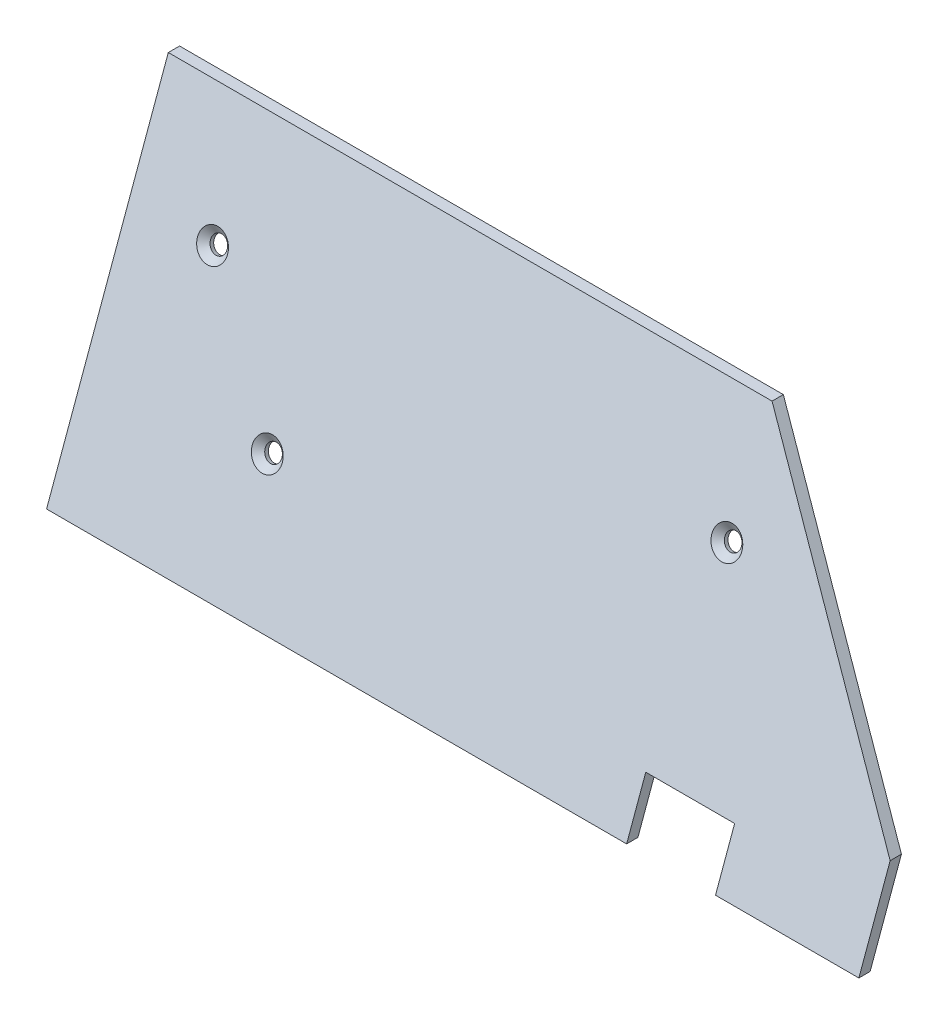
SolidWorks part; units mm, degrees
ref_plane "Front Plane" through (0, 0, 0) normal (0, 0, 1) x (1, 0, 0)
ref_plane "Top Plane" through (0, 0, 0) normal (0, 1, 0) x (1, 0, 0)
ref_plane "Right Plane" through (0, 0, 0) normal (1, 0, 0) x (0, 0, -1)
sketch "Sketch1" plane through (0, 0, 0) normal (1, 0, 0) x (0, 0, -1)
  line L0 (0, 0) -> (-2.3622, 0)
  line L1 (-2.3622, 0) -> (23.1157, 70)
  line L2 (23.1157, 70) -> (25.4779, 70)
  line L3 (25.4779, 70) -> (0, 0)
  dimension "D1" = 2.3622
  dimension "D2" = 2.3622
  dimension "D3" = 70
  dimension "D4" = 70
extrude "Main" add sketch "Sketch1" along normal mid plane 170
hole_wizard "BackBracketHoles" positions "Sketch2" profile "Sketch3" countersink size "M3" standard "ANSI Metric"
sketch "Sketch2" plane through (0, 0.7592, 2.0859) normal (0, 0.342, 0.9397) x (1, 0, 0)
  line L0 (-85, 73.6845) -> (-85, -0.8079) construction
  line L1 (85, -0.8079) -> (-85, -0.8079) construction
  point P0 (-67.6378, 50.0021)
  point P2 (-47.6378, 25.0021)
  dimension "D1" = 17.3622
  dimension "D2" = 50.81
  dimension "D3" = 25.81
  dimension "D4" = 37.3622
sketch "Sketch3" plane through (-67.6378, 47.7458, -15.0158) normal (1, 0, 0) x (0, -0.9397, 0.342)
  line L0 (0, 0) -> (0, 5)
  line L1 (0, 5) -> (1.75, 5)
  line L2 (1.75, 5) -> (1.75, 1.4)
  line L3 (1.75, 1.4) -> (3.15, 0)
  line L5 (3.15, 0) -> (0, 0)
  line L6 (-1.75, 1.4) -> (-3.15, 0) construction
  line L10 (0, 5) -> (-1.75, 5) construction
  line L11 (0, -6.35) -> (0, 107.95) construction
  dimension "Hole Dia." = 3.5
  dimension "Hole Depth" = 5
  dimension "Near C'Sink Dia." = 6.3
  dimension "Near C'Sink Angle" = 90
  dimension "Drill Angle" = 180
sketch "Sketch4" plane through (0, 0, 0) normal (0, 0, 1) x (1, 0, 0)
  line L0 (85.1927, 0.1116) -> (100, 0.1116)
  line L1 (100, 0.1116) -> (41.3567, 70)
  line L2 (85, 70) -> (-85, 70) construction
  line L3 (41.3567, 70) -> (41.3567, 0)
  line L4 (85, 0) -> (-85, 0) construction
  line L5 (41.3567, 0) -> (85.1927, 0.1116)
  line L6 (100, 0.1116) -> (100, 70)
  line L7 (100, 70) -> (41.3567, 70)
  line L8 (85, 70) -> (85, 0) construction
  dimension "D1" = 50
  dimension "D2" = 15
extrude "Cut-Extrude1" cut sketch "Sketch4" against normal blind 28.6 contours L6 L7 L1 region at (80.4522, 46.7039, 0)
hole_wizard "CSK for M3 Flat Head Machine Screw1" positions "Sketch5" profile "Sketch6" countersink size "M3" standard "ANSI Metric"
sketch "Sketch5" plane through (0, 0.7592, 2.0859) normal (0, 0.342, 0.9397) x (1, 0, 0)
  line L0 (30, 60.0021) -> (52.6886, 60.0021) construction
  line L1 (30, 60.0021) -> (30, 32.9616) construction
  point P0 (40, 50.0021)
  dimension "D1" = 10
  dimension "D2" = 10
sketch "Sketch6" plane through (40, 47.7458, -15.0158) normal (1, 0, 0) x (0, -0.9397, 0.342)
  line L0 (0, 0) -> (0, 5)
  line L1 (0, 5) -> (1.75, 5)
  line L2 (1.75, 5) -> (1.75, 1.4)
  line L3 (1.75, 1.4) -> (3.15, 0)
  line L5 (3.15, 0) -> (0, 0)
  line L6 (-1.75, 1.4) -> (-3.15, 0) construction
  line L10 (0, 5) -> (-1.75, 5) construction
  line L11 (0, -6.35) -> (0, 107.95) construction
  dimension "Hole Dia." = 3.5
  dimension "Hole Depth" = 5
  dimension "Near C'Sink Dia." = 6.3
  dimension "Near C'Sink Angle" = 90
  dimension "Drill Angle" = 180
sketch "Sketch7" plane through (0, 0, 0) normal (0, 0, 1) x (1, 0, 0)
  line L0 (36.4, 11.002) -> (36.4, 0.002) construction
  line L1 (36.4, 11.002) -> (55, 11.002)
  line L2 (36.4, 11.002) -> (36.4, 0.002)
  line L3 (36.4, 0.002) -> (55, 0.002)
  line L4 (55, 11.002) -> (55, 0.002)
  line L6 (36.4, 11.002) -> (55, 11.002) construction
  line L7 (36.4, 0.002) -> (55, 0.002)
  line L8 (36.4, 0.002) -> (36.4, -0.998)
  line L9 (36.4, -0.998) -> (55, -0.998)
  line L10 (55, 0.002) -> (55, -0.998)
  dimension "D1" = 1
extrude "Cut-Extrude3" cut sketch "Sketch7" against normal up to surface (29.6367 mm away) from offset 30 contours L10 L3 L8 L9 | L4 L1 L2 L3 region at (45.7, 5.502, 0) region at (45.7, -0.498, 0) up to face at (40, 45.3421, -16.5032)
